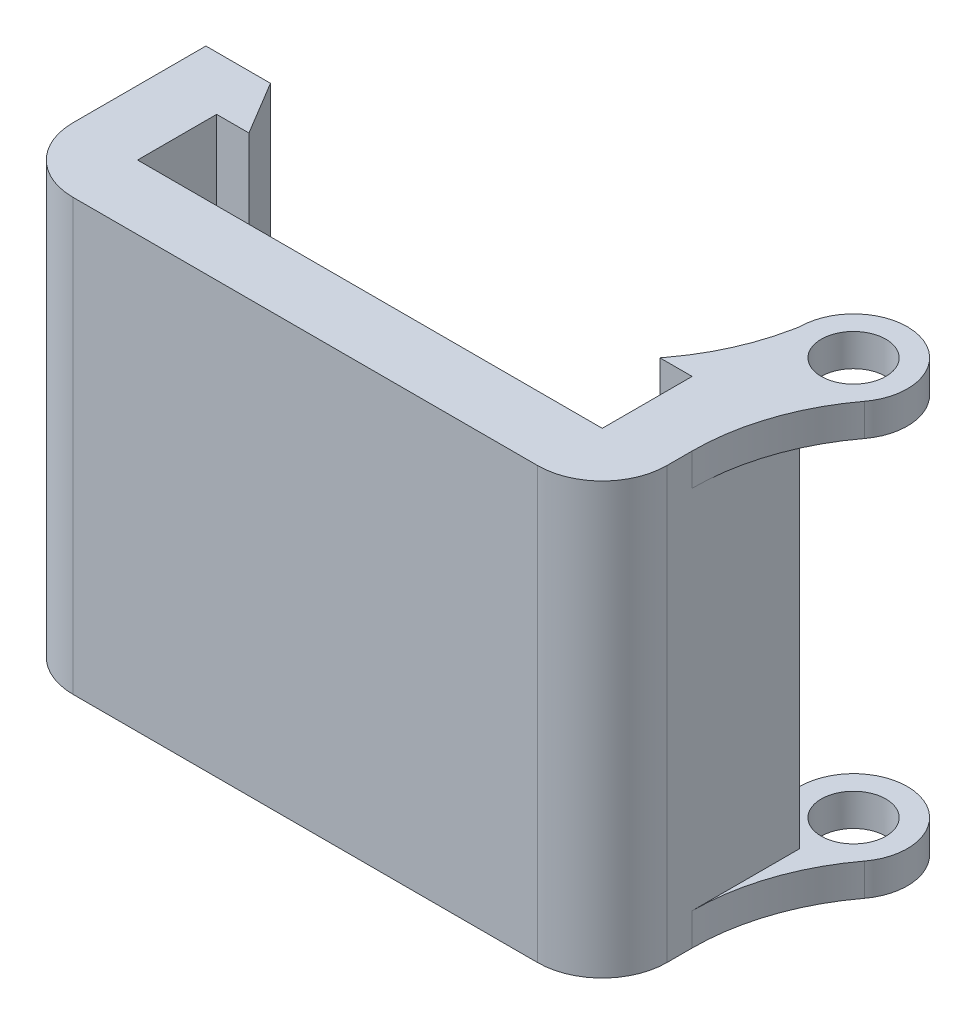
SolidWorks part; units mm, degrees
ref_plane "Front Plane" through (0, 0, 0) normal (0, 0, 1) x (1, 0, 0)
ref_plane "Top Plane" through (0, 0, 0) normal (0, 1, 0) x (1, 0, 0)
ref_plane "Right Plane" through (0, 0, 0) normal (1, 0, 0) x (0, 0, -1)
sketch "Sketch1" plane through (0, 0, 24.175) normal (0, 0, 1) x (1, 0, 0)
  line L0 (-13.795, 75.7847) -> (13.795, 75.7847)
  line L1 (-13.795, 55.7847) -> (13.795, 55.7847)
  line L2 (-13.795, 55.7847) -> (-13.795, 75.7847)
  line L3 (13.795, 55.7847) -> (13.795, 75.7847)
  line L4 (-10.795, 23.495) -> (-10.795, 95.5796) construction
  arc A0 (-3.0486, 76.9696) -> (-76.9008, 4.46) centre (0, 0) ccw construction
  arc A1 (76.9696, 3.0486) -> (4.46, 76.9008) centre (0, 0) ccw construction
  dimension "D1" = 3
  dimension "D2" = 20
extrude "Boss-Extrude1" add sketch "Sketch1" along normal blind 3
sketch "Sketch2" plane through (0, 0, 24.175) normal (0, 0, -1) x (-1, 0, 0)
  line L0 (13.795, 55.7847) -> (-13.795, 55.7847) construction
  line L1 (-13.795, 75.7847) -> (-10.795, 75.7847)
  line L2 (-13.795, 75.7847) -> (-13.795, 55.7847)
  line L3 (-13.795, 55.7847) -> (-10.795, 55.7847)
  line L4 (-10.795, 75.7847) -> (-10.795, 55.7847)
  line L6 (13.795, 75.7847) -> (10.795, 75.7847)
  line L7 (13.795, 75.7847) -> (13.795, 55.7847)
  line L8 (13.795, 55.7847) -> (10.795, 55.7847)
  line L9 (10.795, 75.7847) -> (10.795, 55.7847)
  dimension "D1" = 3
  dimension "D2" = 3
extrude "Boss-Extrude2" add sketch "Sketch2" along normal offset from surface (6.175 mm away) 3 offset beyond the face yes
sketch "Sketch4" plane through (0, 75.7847, 0) normal (0, 1, 0) x (1, 0, 0)
  line L0 (-10.795, -20.5) -> (-10.795, -18)
  line L1 (10.795, -18) -> (10.795, -20)
  line L2 (-10.795, -18) -> (-9.295, -20.5)
  line L3 (-9.295, -20.5) -> (-10.795, -20.5)
  line L4 (-10.795, -18) -> (-10.795, -24.175) construction
  line L5 (142.875, -21) -> (-142.875, -21) construction
  line L6 (10.795, -18) -> (10.795, -24.175) construction
  line L7 (10.795, -20) -> (9.295, -20)
  line L8 (9.295, -20) -> (10.795, -18)
  line L9 (10.9665, -21) -> (-10.9664, -21) construction
  dimension "D1" = 1.5
  dimension "D2" = 0.5
  dimension "D3" = 1.5
  dimension "D4" = 1
extrude "Boss-Extrude3" add sketch "Sketch4" against normal up to surface (20 mm away) up to face at (0, 55.7847, 21.8375)
sketch "Sketch5" plane through (0, 0, 27.175) normal (0, 0, 1) x (1, 0, 0)
  line L0 (-13.795, 55.7847) -> (13.795, 55.7847) construction
  line L1 (13.795, 75.7847) -> (8.795, 75.7847)
  line L2 (13.795, 75.7847) -> (13.795, 55.7847)
  line L3 (13.795, 55.7847) -> (8.795, 55.7847)
  line L4 (8.795, 75.7847) -> (8.795, 55.7847)
  dimension "D1" = 5
extrude "Boss-Extrude4" [suppressed] add sketch "Sketch5" along normal blind 6
sketch "Sketch6" plane through (0, 55.7847, 0) normal (0, -1, 0) x (1, 0, 0)
  line L0 (13.795, 18) -> (10.795, 18) construction
  line L1 (13.795, 18) -> (13.795, 15.5) construction
  line L2 (10.795, 18) -> (11.295, 15.5)
  line L3 (10.795, 18) -> (13.795, 18)
  arc A0 (11.295, 15.5) -> (13.795, 18) centre (13.795, 15.5) ccw
  dimension "D1" = 5
extrude "Boss-Extrude5" add sketch "Sketch6" against normal blind 1.5
sketch "Sketch7" plane through (0, 75.7847, 0) normal (0, 1, 0) x (1, 0, 0)
  line L0 (10.795, -18) -> (11.295, -15.5)
  line L1 (10.795, -18) -> (13.795, -18)
  circle A0 centre (13.795, -15.5) radius 2.5 construction
  arc A1 (13.795, -18) -> (11.295, -15.5) centre (13.795, -15.5) ccw
extrude "Boss-Extrude6" add sketch "Sketch7" against normal blind 1.5
sketch "Sketch8" plane through (0, 75.7847, 0) normal (0, 1, 0) x (1, 0, 0)
  circle A0 centre (13.795, -15.5) radius 1.5
  circle A1 centre (13.795, -15.5) radius 1 construction
  dimension "D1" = 0.5
extrude "Cut-Extrude1" cut sketch "Sketch8" against normal up to surface (20 mm away) up to face at (1.101, 55.7847, 20.6294)
sketch "Sketch9" [suppressed] plane through (13.795, 0, 0) normal (1, 0, 0) x (0, 0, -1)
  line L0 (-33.175, 55.7847) -> (-33.175, 75.7847) construction
  line L1 (-33.175, 74.2847) -> (-15, 74.2847)
  line L2 (-33.175, 74.2847) -> (-33.175, 57.2847)
  line L3 (-33.175, 57.2847) -> (-15, 57.2847)
  line L4 (-15, 74.2847) -> (-15, 57.2847)
  point P7 (0, 0)
  point P9 (0, 0)
  point P10 (0, 0)
  point P11 (0, 0)
  dimension "D1" = 18.175
  dimension "D2" = 17
extrude "Cut-Extrude2" [suppressed] cut sketch "Sketch9" against normal blind 1
fillet "Fillet1" radius 10 2 edges at (13.795, 56.5347, 18) (13.795, 75.0347, 18)
fillet "Fillet2" radius 10 2 edges at (10.795, 56.5347, 18) (10.795, 75.0347, 18)
fillet "Fillet3" [suppressed] radius 3
fillet "Fillet4" radius 3 2 edges at (-13.795, 65.7847, 27.175) (13.795, 65.7847, 27.175)
